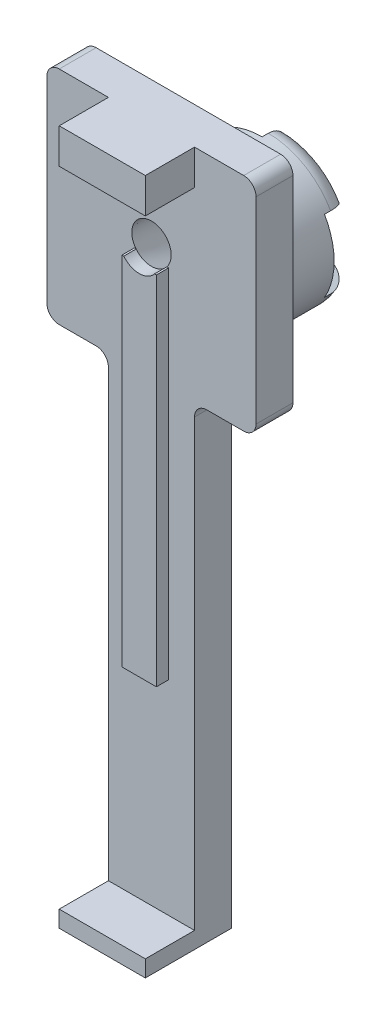
SolidWorks part; units mm, degrees
ref_plane "Front Plane" through (0, 0, 0) normal (0, 0, 1) x (1, 0, 0)
ref_plane "Top Plane" through (0, 0, 0) normal (0, 1, 0) x (1, 0, 0)
ref_plane "Right Plane" through (0, 0, 0) normal (1, 0, 0) x (0, 0, -1)
sketch "Sketch1" plane through (0, 0, 0) normal (0, 0, 1) x (1, 0, 0)
  line L7 (3.5, -18.4549) -> (-3.5, -18.4549)
  line L8 (3.5, -18.4549) -> (3.5, 38.0451)
  line L9 (3.5, 38.0451) -> (-3.5, 38.0451)
  line L10 (-3.5, -18.4549) -> (-3.5, 38.0451)
  line L11 (3.5, -18.4549) -> (-3.5, 38.0451) construction
  line L12 (3.5, 38.0451) -> (-3.5, -18.4549) construction
  point P6 (0, 9.7951)
  dimension "D3" = 56.5
  dimension "D4" = 7
extrude "Boss-Extrude1" add sketch "Sketch1" along normal blind 3
sketch "Sketch2" plane through (0, 0, 3) normal (0, 0, 1) x (1, 0, 0)
  line L0 (3.5, -18.4549) -> (-3.5, -18.4549) construction
  line L1 (0, -0.5049) -> (0, -18.4549) construction
  line L16 (-1.4, -0.5049) -> (1.4, -0.5049)
  line L17 (-1.4, 28.4951) -> (-1.4, -0.5049)
  line L18 (1.4, 28.4951) -> (-1.4, 28.4951)
  line L19 (1.4, -0.5049) -> (1.4, 28.4951)
  point P0 (0, -0.5049)
  dimension "D1" = 17.95
  dimension "D2" = 29
  dimension "D3" = 2.8
extrude "Boss-Extrude2" add sketch "Sketch2" along normal blind 1
sketch "Sketch3" plane through (0, 0, 3) normal (0, 0, 1) x (1, 0, 0)
  line L0 (3.5, -18.4549) -> (3.5, 38.0451) construction
  line L1 (-3.5, 38.0451) -> (3.5, 38.0451)
  line L2 (-3.5, 38.0451) -> (-3.5, 35.1951)
  line L3 (-3.5, 35.1951) -> (3.5, 35.1951)
  line L4 (3.5, 38.0451) -> (3.5, 35.1951)
  line L5 (-3.5, -18.4549) -> (-3.5, 38.0451) construction
  line L6 (3.5, -18.4549) -> (-3.5, -18.4549)
  line L7 (3.5, -18.4549) -> (3.5, -17.1049)
  line L8 (3.5, -17.1049) -> (-3.5, -17.1049)
  line L9 (-3.5, -18.4549) -> (-3.5, -17.1049)
  dimension "D1" = 2.85
  dimension "D2" = 1.35
extrude "Boss-Extrude3" add sketch "Sketch3" along normal blind 4
sketch "Sketch4" plane through (-3.5, 0, 0) normal (-1, 0, 0) x (0, 0, 1)
  line L0 (3, -17.1049) -> (3, 35.1951) construction
  line L1 (0, 38.0451) -> (3, 38.0451)
  line L2 (0, 38.0451) -> (0, 20.0451)
  line L3 (0, 20.0451) -> (3, 20.0451)
  line L4 (3, 38.0451) -> (3, 20.0451)
  dimension "D1" = 18
extrude "Boss-Extrude4" add sketch "Sketch4" along normal blind 5
sketch "Sketch5" plane through (3.5, 0, 0) normal (1, 0, 0) x (0, 0, -1)
  line L4 (0, 38.0451) -> (-3, 38.0451)
  line L5 (-3, 38.0451) -> (-3, 20.0451)
  line L6 (-3, 20.0451) -> (0, 20.0451)
  line L7 (0, 20.0451) -> (0, 38.0451)
  line L8 (0, 38.0451) -> (-3, 38.0451)
  line L9 (-3, 38.0451) -> (-3, 20.0451)
  line L10 (-3, 20.0451) -> (0, 20.0451)
  line L11 (0, 20.0451) -> (0, 38.0451)
  dimension "D1" = 0
extrude "Boss-Extrude5" add sketch "Sketch5" along normal blind 5
sketch "Sketch7" plane through (0, 0, 3) normal (0, 0, 1) x (1, 0, 0)
  line L0 (-1.4, -0.5049) -> (1.4, -0.5049) construction
  circle A0 centre (0, 29.4951) radius 1.6
  dimension "D1" = 3.2
  dimension "D2" = 30
sketch "Sketch9" plane through (0, 0, 0) normal (0, 0, -1) x (-1, 0, 0)
  line L0 (0, 38.0451) -> (0, -18.4549) construction
  line L1 (-8.5, 38.0451) -> (8.5, 38.0451) construction
  line L2 (-3.5, -18.4549) -> (3.5, -18.4549) construction
  circle A0 centre (0, 26.6701) radius 5.85
  dimension "D1" = 11.7
  dimension "D2" = 11.375
extrude "Boss-Extrude7" add sketch "Sketch9" along normal blind 8
sketch "Sketch10" plane through (0, 0, -8) normal (0, 0, -1) x (-1, 0, 0)
  line L0 (0, 32.5201) -> (0, 20.8201)
  line L1 (-5.0662, 29.5951) -> (5.0662, 23.7451)
  line L2 (5.0662, 29.5951) -> (-5.0662, 23.7451)
  circle A3 centre (0, 26.6701) radius 5.85
  circle A4 centre (0, 26.6701) radius 5.85 construction
  circle M5 centre (0, 26.6701) radius 5.85
  dimension "D1" = 60
  dimension "D2" = 60
fillet "Fillet1" radius 1.5 1 edges at (-5.85, 26.6701, -8)
fillet "Fillet2" radius 1 6 edges at (-3.5, 20.0451, 1.5) (-8.5, 20.0451, 1.5) (-8.5, 38.0451, 1.5) (3.5, 20.0451, 1.5) (8.5, 38.0451, 1.5) (8.5, 20.0451, 1.5)
sketch "Sketch11" plane through (0, 0, -8) normal (0, 0, -1) x (-1, 0, 0)
  circle A0 centre (0, 26.6701) radius 3.4369
ref_plane "Plane1" through (0, 0, 0) normal (1, 0, 0) x (0, 0, -1)
loft "Cut-Loft6" cut profiles "Sketch11", "Sketch7"
extrude "Cut-Extrude5" cut sketch "Sketch10" against normal blind 2 contours L2 L1 M5 | L2 L0 M5 | L1 L0 M5
sketch "Sketch14" plane through (0, 0, 3) normal (0, 0, 1) x (1, 0, 0)
  circle A0 centre (0, 29.4951) radius 1.6
  circle A1 centre (0, 29.4951) radius 1.6 construction
extrude "Cut-Extrude6" cut sketch "Sketch14" along normal blind 3
